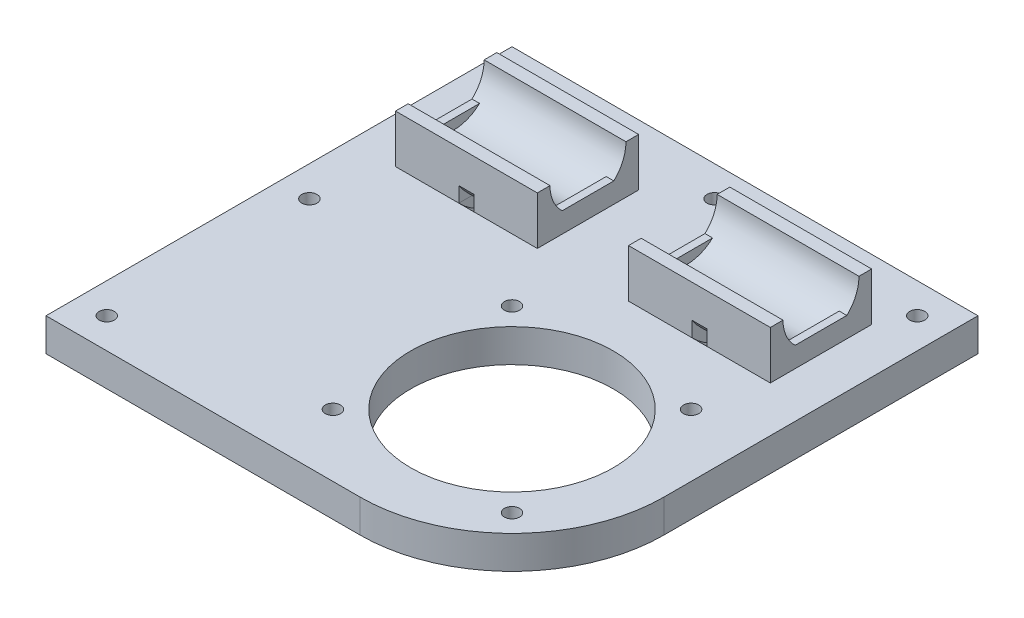
SolidWorks part; units mm, degrees
ref_plane "Front Plane" through (0, 0, 0) normal (0, 0, 1) x (1, 0, 0)
ref_plane "Top Plane" through (0, 0, 0) normal (0, 1, 0) x (1, 0, 0)
ref_plane "Right Plane" through (0, 0, 0) normal (1, 0, 0) x (0, 0, -1)
sketch "Sketch7" plane through (0, 0, 0) normal (0, 1, 0) x (1, 0, 0)
  line L0 (-46, -46) -> (16, -46)
  line L1 (-46, 46) -> (46, 46)
  line L2 (-46, 46) -> (-46, -46)
  line L3 (46, -16) -> (46, 46)
  arc A0 (46, -16) -> (16, -46) centre (16, -16) cw
  circle A1 centre (16, -16) radius 20
  circle A2 centre (-1.6777, 1.6777) radius 1.5
  circle A3 centre (-40, 40) radius 1.5
  circle A4 centre (-40, -40) radius 1.5
  circle A5 centre (40, 40) radius 1.5
  circle A6 centre (0, 40) radius 1.5
  circle A7 centre (-40, 0) radius 1.5
  circle A10 centre (33.6777, 1.6777) radius 1.5
  circle A12 centre (33.6777, -33.6777) radius 1.5
  circle A14 centre (-1.6777, -33.6777) radius 1.5
  circle A15 centre (16, 9) radius 1.5 [skipped]
  circle A16 centre (-9, -16) radius 1.5 [skipped]
  circle A17 centre (16, -41) radius 1.5 [skipped]
  circle A18 centre (41, -16) radius 1.5 [skipped]
extrude "Extrude2" add sketch "Sketch7" along normal blind 4 and the other way blind 2.5
sketch "Sketch8" plane through (0, 4, 0) normal (0, 1, 0) x (1, 0, 0)
  line L0 (-46, 66.843) -> (47.0843, 66.843)
  line L1 (-46, 46) -> (-46, -46) construction
  line L3 (-46, 14) -> (46, 14)
  line L4 (-46, 34) -> (46, 34)
  line L5 (-37, 34) -> (-37, 14)
  line L6 (-9, 34) -> (-9, 14)
  line L7 (9, 34) -> (9, 14)
  line L8 (37, 34) -> (37, 14)
extrude "Extrude3" add sketch "Sketch8" along normal blind 9.5 separate body contours L6 region at (-23, 4, -24)
sketch "Sketch10" plane through (-9, 0, 0) normal (1, 0, 0) x (0, 0, -1)
  line L0 (34, 13.5) -> (14, 13.5) construction
  line L1 (24, 13.5) -> (49.4193, 500000)
  line L4 (29.099, 8) -> (18.901, 8)
  circle A0 centre (24, 13.5) radius 7.5
  line M3 (34, 13.5) -> (14, 13.5)
extrude "Extrude6" cut sketch "Sketch10" against normal blind 28 contours A0 L4 M3 region at (-9, 10.906, -24)
ref_plane "Plane3" through (-35.5, 0, 0) normal (-1, 0, 0) x (0, 0, 1)
sketch "Sketch15" plane through (-35.5, 0, 0) normal (-1, 0, 0) x (0, 0, 1)
  circle A0 centre (-24, 13.5) radius 7.5
extrude "Extrude7" cut sketch "Sketch15" against normal blind 25
sketch "Sketch16" plane through (0, 0, -14) normal (0, 0, 1) x (1, 0, 0)
  line L0 (-37, 4) -> (-9, 4) construction
  line L1 (-24.5, 4) -> (-21.5, 4)
  line L3 (-21.5, 7) -> (-21.5, 4)
  line L4 (-21.5, 7) -> (-24.5, 7)
  line L5 (-24.5, 7) -> (-24.5, 4)
ref_plane "Plane4" through (-23, 0, 0) normal (1, 0, 0) x (0, 0, -1)
sketch "Sketch17" plane through (-23, 0, 0) normal (1, 0, 0) x (0, 0, -1)
  circle A0 centre (24, 13.5) radius 12.8062
sweep "Cut-Sweep1" cut profiles "Sketch16" path "Sketch17"
extrude "Extrude8" add sketch "Sketch8<4>" along normal blind 9.5 contours L8 L4 L7 L3 region at (23, 4, -24)
sketch "Sketch8<4>" plane through (0, 4, 0) normal (0, 1, 0) x (1, 0, 0) same geometry as "Sketch8"
sketch "Sketch18" plane through (37, 0, 0) normal (1, 0, 0) x (0, 0, -1)
  line L0 (34, 13.5) -> (14, 13.5) construction
  line L3 (29.099, 8) -> (18.901, 8)
  circle A0 centre (24, 13.5) radius 7.5
  line M3 (34, 13.5) -> (14, 13.5)
extrude "Extrude9" cut sketch "Sketch18" against normal blind 28 contours A0 L3 M3 region at (37, 10.906, -24)
ref_plane "Plane5" through (35.5, 0, 0) normal (1, 0, 0) x (0, 0, -1)
sketch "Sketch19" plane through (35.5, 0, 0) normal (1, 0, 0) x (0, 0, -1)
  circle A0 centre (24, 13.5) radius 7.5
extrude "Extrude10" cut sketch "Sketch19" against normal blind 25
sketch "Sketch20" plane through (0, 0, -14) normal (0, 0, 1) x (1, 0, 0)
  line L0 (21.5, 7) -> (24.5, 7)
  line L1 (9, 4) -> (37, 4) construction
  line L3 (24.5, 7) -> (24.5, 4)
  line L4 (24.5, 4) -> (21.5, 4)
  line L5 (21.5, 4) -> (21.5, 7)
ref_plane "Plane6" through (23, 0, 0) normal (1, 0, 0) x (0, 0, -1)
sketch "Sketch21" plane through (23, 0, 0) normal (1, 0, 0) x (0, 0, -1)
  circle A0 centre (24, 13.5) radius 12.8062
sweep "Cut-Sweep2" cut profiles "Sketch20" path "Sketch21"
